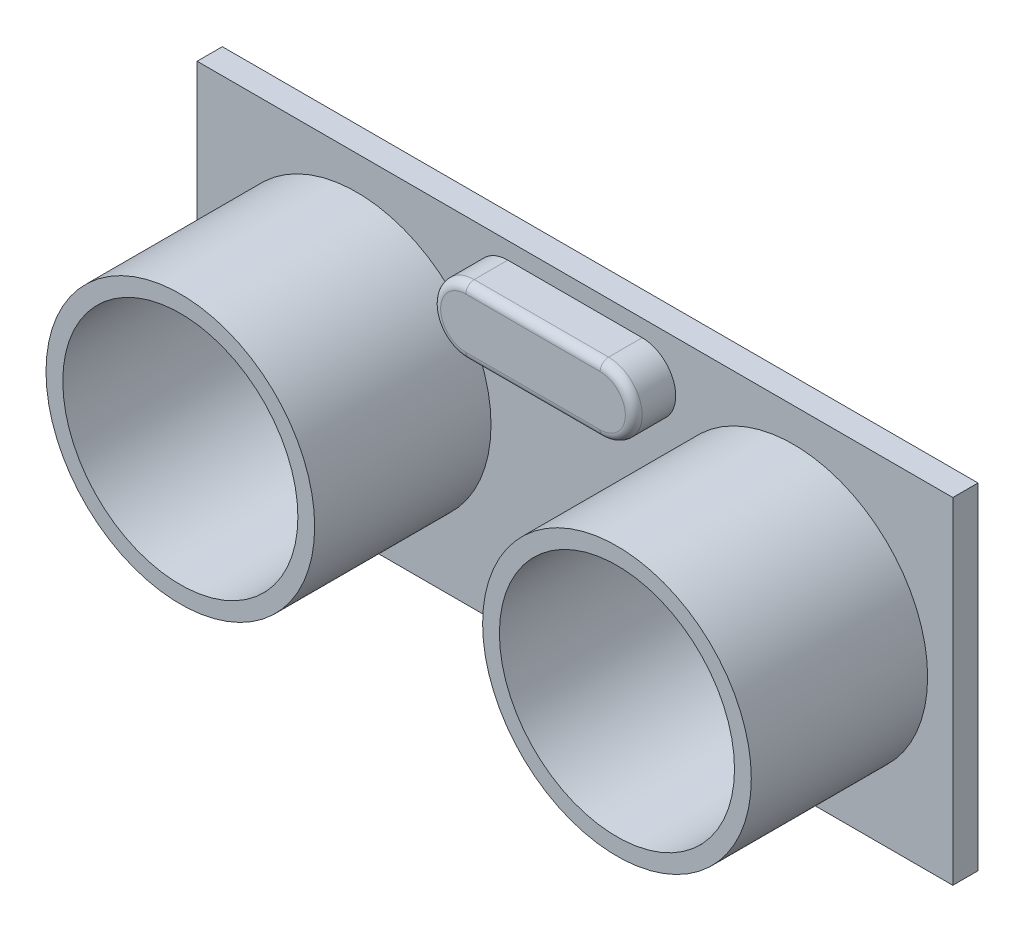
SolidWorks part; units mm, degrees
ref_plane "Front Plane" through (0, 0, 0) normal (0, 0, 1) x (1, 0, 0)
ref_plane "Top Plane" through (0, 0, 0) normal (0, 1, 0) x (1, 0, 0)
ref_plane "Right Plane" through (0, 0, 0) normal (1, 0, 0) x (0, 0, -1)
sketch "Sketch1" plane through (0, 0, 0) normal (0, 0, 1) x (1, 0, 0)
  line L0 (0, 0) -> (0, 14.174) construction
  line L1 (-22.5, -10) -> (22.5, -10)
  line L2 (-22.5, -10) -> (-22.5, 10)
  line L3 (-22.5, 10) -> (22.5, 10)
  line L4 (22.5, -10) -> (22.5, 10)
  line L5 (-22.5, -10) -> (22.5, 10) construction
  line L6 (-22.5, 10) -> (22.5, -10) construction
  line L7 (-4, 6.9918) -> (4, 6.9918) construction
  line L8 (-4, 8.9918) -> (4, 8.9918)
  line L9 (-4, 4.9918) -> (4, 4.9918)
  circle A0 centre (13, 0) radius 8
  circle A1 centre (-13, 0) radius 8
  circle A2 centre (13, 0) radius 7
  circle A3 centre (-13, 0) radius 7
  arc A4 (-4, 8.9918) -> (-4, 4.9918) centre (-4, 6.9918) ccw
  arc A5 (4, 4.9918) -> (4, 8.9918) centre (4, 6.9918) ccw
  point P0 (0, 0)
  point P18 (0, 6.9918)
  dimension "D3" = 13
  dimension "D7" = 2
  dimension "D1" = 45
  dimension "D2" = 20
  dimension "D6" = 8
  dimension "D4" = 1
  dimension "D5" = 1
extrude "Boss-Extrude1" add sketch "Sketch1" along normal blind 12 contours A1 A3 | A0 A2 region at (5.2263, 0, 0) region at (-20.7737, 0, 0)
extrude "Boss-Extrude2" add sketch "Sketch1<4>" along normal blind 1.5 contours L1 L4 L3 L2 A5 L9 A4 L8 A0 A1 region at (0, -0.6874, 0)
sketch "Sketch1<4>" plane through (0, 0, 0) normal (0, 0, 1) x (1, 0, 0) same geometry as "Sketch1"
extrude "Boss-Extrude3" add sketch "Sketch1<5>" along normal blind 4 contours L9 A5 L8 A4 region at (0, 6.9918, 0)
sketch "Sketch1<5>" plane through (0, 0, 0) normal (0, 0, 1) x (1, 0, 0) same geometry as "Sketch1"
fillet "Fillet1" radius 0.5 4 edges at (-6, 6.9918, 4) (0, 4.9918, 4) (6, 6.9918, 4) (0, 8.9918, 4)
sketch "Sketch2" plane through (0, 0, 0) normal (0, 0, -1) x (-1, 0, 0)
  line L0 (-22.5, -10) -> (-22.5, 10) construction
  line L1 (3, -6.0566) -> (4, -6.0566)
  line L2 (2.5, -6.5566) -> (2.5, -7.5566)
  line L3 (3, -8.0566) -> (4, -8.0566)
  line L4 (4.5, -6.5566) -> (4.5, -7.5566)
  arc A0 (2.5, -7.5566) -> (3, -8.0566) centre (3, -7.5566) ccw
  arc A1 (4, -8.0566) -> (4.5, -7.5566) centre (4, -7.5566) ccw
  arc A2 (4, -6.0566) -> (4.5, -6.5566) centre (4, -6.5566) cw
  arc A3 (3, -6.0566) -> (2.5, -6.5566) centre (3, -6.5566) ccw
  point P6 (2.5, -8.0566)
  point P11 (4.5, -6.0566)
  point P14 (2.5, -6.0566)
  dimension "D3" = 0.5
  dimension "D1" = 2
  dimension "D2" = 2
  dimension "D4" = 25
extrude "Boss-Extrude5" add sketch "Sketch2" along normal blind 2
pattern_linear "LPattern1" count 4 spacing 2 along (1, 0, 0) of "Boss-Extrude5"
ref_plane "Plane5" through (2.5, 0, 0) normal (1, 0, 0) x (0, 0, -1)
sketch "Sketch9" plane through (2.5, 0, 0) normal (1, 0, 0) x (0, 0, -1)
  line L0 (2, -7.0566) -> (2.1, -7.0566)
  line L1 (2.5, -7.4566) -> (2.5, -13.0566)
  line L2 (2, -6.5566) -> (2, -7.5566) construction
  arc A0 (2.1, -7.0566) -> (2.5, -7.4566) centre (2.1, -7.4566) cw
  point P7 (2.5, -7.0566)
  dimension "D4" = 0.4
  dimension "D1" = 0.5
  dimension "D2" = 6
  dimension "D3" = 0
sketch "Sketch10" plane through (0, 0, -2) normal (0, 0, -1) x (-1, 0, 0)
  circle A0 centre (-2.5, -7.0566) radius 0.2
sweep "Sweep1" add profiles "Sketch10" path "Sketch9"
pattern_linear "LPattern2" count 4 spacing 2 along (-1, 0, 0) of "Sweep1"
